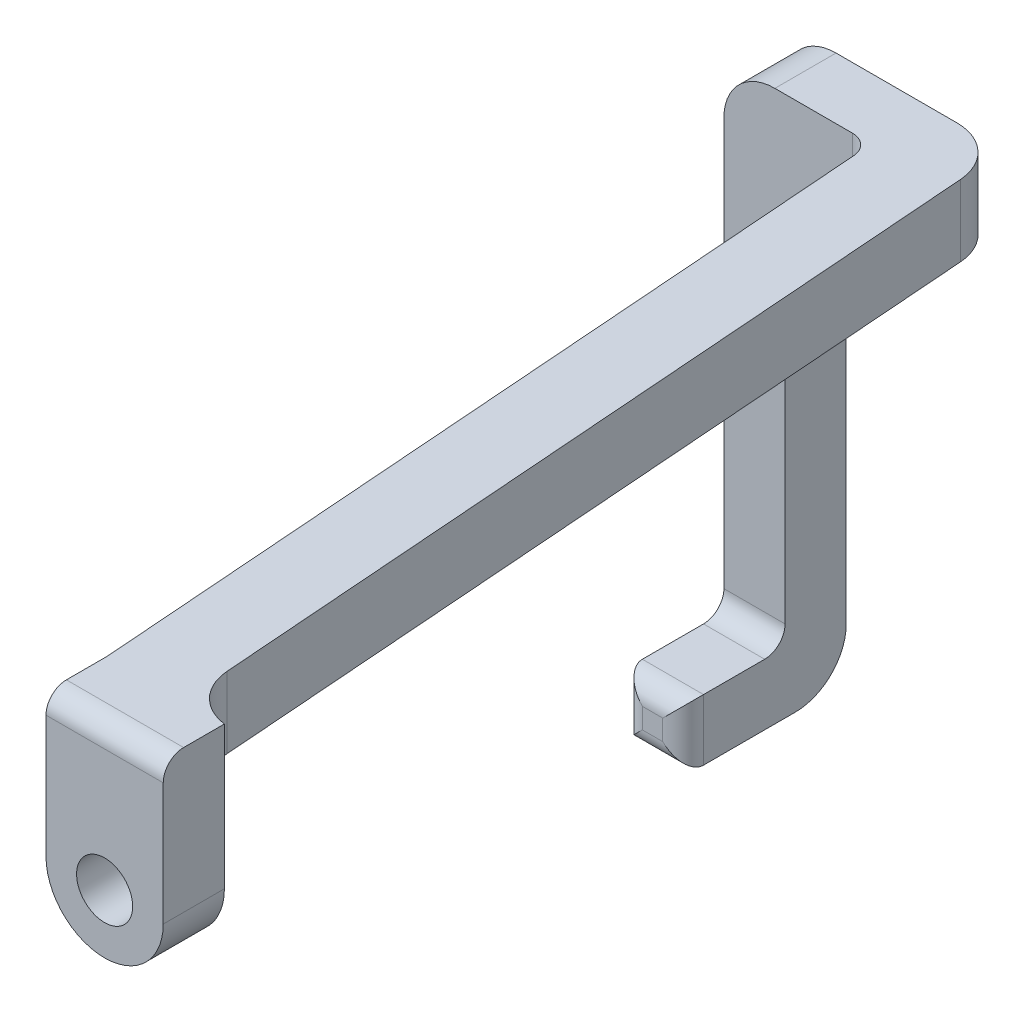
SolidWorks part; units mm, degrees
ref_plane "Front Plane" through (0, 0, 0) normal (1, 0, 0) x (0, 1, 0)
ref_plane "Top Plane" through (0, 0, 0) normal (0, 0, 1) x (0, 1, 0)
ref_plane "Right Plane" through (0, 0, 0) normal (0, 1, 0) x (-1, 0, 0)
sketch "Sketch1" plane through (0, 0, 0) normal (0, 0, 1) x (0, 1, 0)
  line L0 (0, 0) -> (1.375, 0) construction
  line L3 (0, 2.875) -> (7, 2.875)
  line L4 (0, -2.875) -> (7, -2.875)
  line L5 (7, -2.875) -> (7, 2.875)
  arc A0 (0, 2.875) -> (0, -2.875) centre (0, 0) ccw
  circle A3 centre (0, 0) radius 1.375
  point P2 (0, 0)
  dimension "D1" = 2.75
  dimension "D2" = 2.875
  dimension "D3" = 7
extrude "Boss-Extrude1" add sketch "Sketch1" along normal blind 3
sketch "Sketch2" plane through (0, 0, 0) normal (0, 0, -1) x (1, 0, 0)
  line L0 (2.875, -7) -> (-2.875, -7) construction
  line L1 (0.875, -7) -> (-2.875, -7)
  line L2 (2.875, 0) -> (2.875, -7) construction
  line L3 (-2.875, -7) -> (-2.875, 0) construction
  line L4 (0.875, -3.5) -> (0.875, -7)
  line L5 (-2.875, -7) -> (-2.875, -3.5)
  line L6 (-2.875, -3.5) -> (0.875, -3.5)
  dimension "D1" = 2
ref_plane "Plane1" through (0, 0, -43.5) normal (0, 0, -1) x (-1, 0, 0)
sketch "Sketch8" plane through (0, 0, -43.5) normal (0, 0, -1) x (-1, 0, 0)
  line L0 (-0.875, 3.5) -> (-0.875, 7) construction
  line L1 (2.875, 3.5) -> (-0.875, 3.5) construction
  line L2 (2.875, 7) -> (2.875, 3.5) construction
  line L3 (-0.875, 7) -> (2.875, 7) construction
  line L4 (-0.875, 3.5) -> (-0.875, 7) construction
  line L5 (2.875, 3.5) -> (-0.875, 3.5) construction
  line L6 (2.875, 7) -> (2.875, 3.5) construction
  line L7 (-0.875, 7) -> (2.875, 7) construction
  line L8 (2.375, 3.5) -> (2.375, 7)
  line L9 (6.125, 3.5) -> (6.125, 7)
  line L10 (2.375, 7) -> (6.125, 7)
  line L11 (6.125, 3.5) -> (2.375, 3.5)
  dimension "D1" = 3.25
loft "Loft1" add profiles "Sketch2", "Sketch8" connector at (0.875, 3.5, 0) connector at (-2.375, 3.5, -43.5)
sketch "Sketch9" plane through (0, 0, 0) normal (1, 0, 0) x (0, 1, 0)
  line L0 (3.5, 0) -> (3.5, -43.5) construction
  line L1 (7, 0) -> (7, -43.5) construction
  line L2 (3.5, -40.5) -> (3.5, -43.5)
  line L3 (7, -40.5) -> (7, -43.5)
  line L4 (7, -43.5) -> (3.5, -43.5)
  line L6 (7, -40.5) -> (3.5, -40.5)
  dimension "D1" = 3
extrude "Boss-Extrude2" add sketch "Sketch9" against normal blind 7 and the other way up to surface from vertex other way up to face at (-3.6875, 4.8125, -10.875) starting at point (-6.125, 7, -43.5)
sketch "Sketch10" plane through (0, 7, 0) normal (0, 1, 0) x (-1, 0, 0)
  line L0 (13.125, -43.5) -> (6.125, -43.5) construction
  line L1 (13.125, -43.5) -> (13.125, -40.5) construction
  line L2 (5.9009, -40.5) -> (13.125, -40.5) construction
  line L3 (13.125, -43.5) -> (10.125, -43.5)
  line L4 (13.125, -43.5) -> (13.125, -40.5)
  line L5 (10.125, -40.5) -> (13.125, -40.5)
  line L6 (10.125, -40.5) -> (10.125, -43.5)
  dimension "D1" = 3
extrude "Boss-Extrude3" add sketch "Sketch10" against normal blind 23 from surface starting at face at (-5.609, 3.5, -24.2143)
sketch "Sketch11" plane through (0, 0, -40.5) normal (0, 0, 1) x (1, 0, 0)
  line L0 (-13.125, -19.5) -> (-13.125, 7) construction
  line L2 (-10.125, -19.5) -> (-10.125, 3.5) construction
  line L3 (-13.125, -16.5) -> (-13.125, -19.5)
  line L4 (-13.125, -16.5) -> (-10.125, -16.5)
  line L5 (-10.125, -16.5) -> (-10.125, -19.5)
  line L6 (-10.125, -19.5) -> (-13.125, -19.5)
  line L7 (-13.125, -19.5) -> (-10.125, -19.5) construction
  dimension "D1" = 3
extrude "Boss-Extrude4" add sketch "Sketch11" along normal blind 5
fillet "Fillet1" radius 2.5 5 edges at (-11.625, -19.5, -43.5) (-10.125, 3.5, -42) (-13.125, 7, -42)
fillet "Fillet2" radius 1 8 edges at (-10.125, -18, -35.5) (-11.625, -19.5, -35.5) (-13.125, -18, -35.5) (-11.625, -16.5, -35.5) (0, 7, 3) (-5.9009, 5.25, -40.5) (-11.625, -16.5, -40.5)
